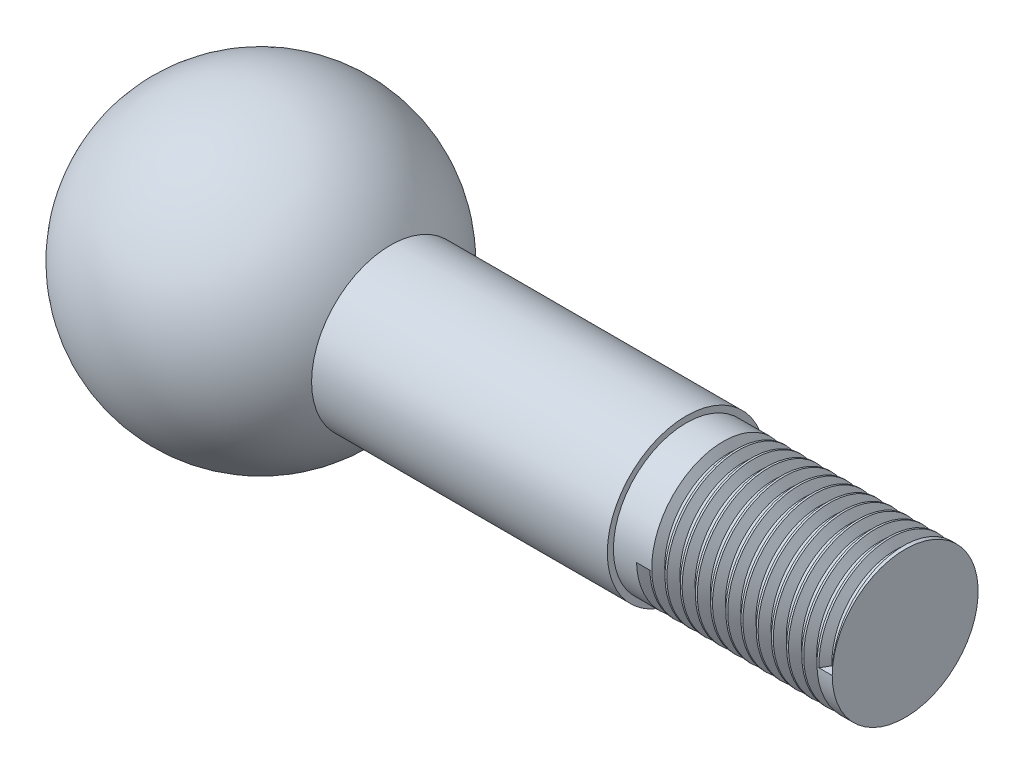
SolidWorks part; units mm, degrees
ref_plane "Front Plane" through (0, 0, 0) normal (0, 0, 1) x (1, 0, 0)
ref_plane "Top Plane" through (0, 0, 0) normal (0, 1, 0) x (1, 0, 0)
ref_plane "Right Plane" through (0, 0, 0) normal (1, 0, 0) x (0, 0, -1)
sketch "Sketch1" plane through (0, 0, 0) normal (0, 0, 1) x (1, 0, 0)
  line L0 (0, 27.1194) -> (0, -3.1035)
  arc A0 (0, 25) -> (0, 0) centre (0, 12.5) cw
revolve "Revolve1" add sketch "Sketch1" angle 360 about L0 region at (5.3052, 12.5, 0)
sketch "Sketch2" plane through (0, 0, 0) normal (1, 0, 0) x (0, 0, -1)
  line L0 (0, 0) -> (0, 25)
  circle A0 centre (0, 12.5) radius 12.5 construction
  circle A1 centre (0, 12.5) radius 6.5
  dimension "D1" = 13
extrude "Boss-Extrude1" add sketch "Sketch2" along normal blind 35 contours A1
sketch "Sketch3" plane through (35, 0, 0) normal (1, 0, 0) x (0, 0, -1)
  circle A0 centre (0, 12.5) radius 6
  dimension "D1" = 12
extrude "Boss-Extrude2" add sketch "Sketch3" along normal blind 18
thread "Thread1" pitch 1.25 method cut profile "Thread Profile1" start angle 0, offset 0, length 15, pitch 1.25, diameter 12
ref_plane "Plane1" through (53, 12.5, 6) normal (0, -1, 0) x (0, 0, 1)
sketch "Thread Profile1" plane through (53, 12.5, 6) normal (0, -1, 0) x (0, 0, 1)
  line L0 (0, 0) -> (0, 1.25) construction
  line L11 (0, 0) -> (0, 1.0937)
  line L12 (0, 1.0937) -> (-0.6766, 0.7031)
  line L13 (-0.6766, 0.7031) -> (-0.6766, 0.3906)
  line L15 (-0.6766, 0.3906) -> (0, 0)
  line L17 (-0.6766, 0.5469) -> (0, 0.5469) construction
  point P2 (0, 0)
  dimension "Pitch" = 1.25
  dimension "Profile_Angle" = 60
  dimension "Profile_Land" = 0.3125
  dimension "Profile_Height" = 0.6766
